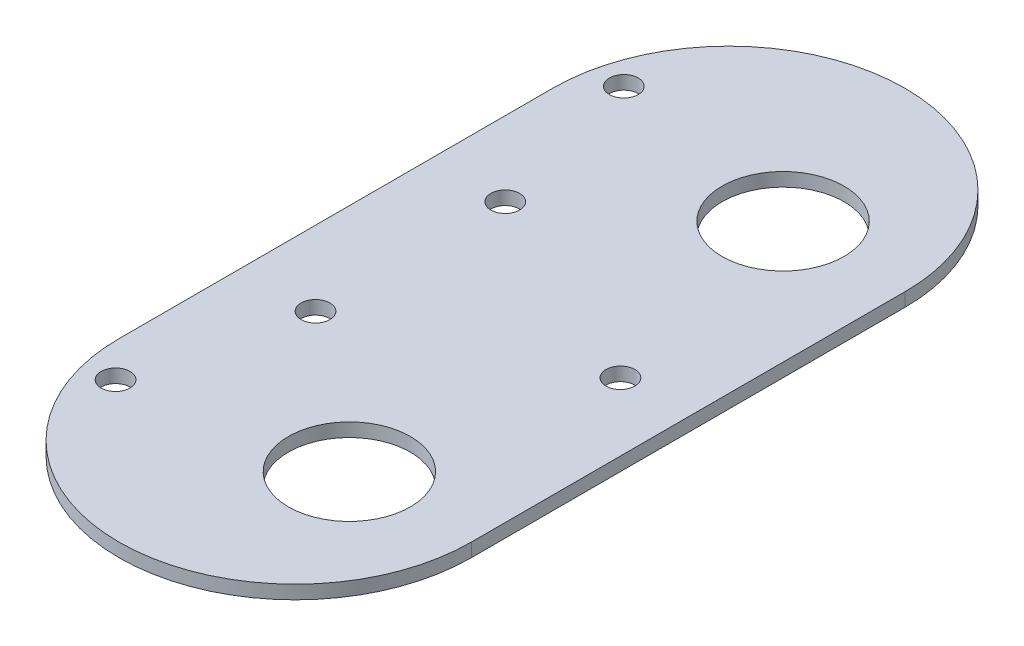
SolidWorks part; units mm, degrees
material "6061-T6 (SS)"
ref_plane "Front" through (0, 0, 0) normal (0, 0, 1) x (1, 0, 0)
ref_plane "Top" through (0, 0, 0) normal (0, 1, 0) x (1, 0, 0)
ref_plane "Right" through (0, 0, 0) normal (1, 0, 0) x (0, 0, -1)
sketch "Sketch1" plane through (0, 0, 0) normal (0, 1, 0) x (1, 0, 0)
  line L0 (0, 50.8) -> (0, -50.8) construction
  line L1 (-53.9705, 50.8) -> (-53.9705, -50.8)
  line L2 (28.5705, 50.8) -> (28.5705, -50.8)
  circle A0 centre (0, 50.8) radius 14.2875
  circle A1 centre (0, -50.8) radius 14.2875
  circle A4 centre (0, 50.8) radius 38.1 construction
  circle A5 centre (0, -50.8) radius 38.1 construction
  arc A6 (-53.9705, -50.8) -> (28.5705, -50.8) centre (-12.7, -50.8) ccw
  arc A7 (-53.9705, 50.8) -> (28.5705, 50.8) centre (-12.7, 50.8) cw
  point P4 (0, 0)
  dimension "D2" = 28.575
  dimension "D3" = 41.2705
  dimension "D4" = 76.2
  dimension "D1" = 101.6
  dimension "D5" = 12.7
extrude "Boss-Extrude1" add sketch "Sketch1" along normal blind 3.175
hole_wizard "1/4 Clearance Hole1" positions "Sketch2" profile "Sketch3" hole size "1/4" standard "ANSI Inch"
sketch "Sketch2" plane through (0, 3.175, 0) normal (0, 1, 0) x (1, 0, 0)
  line L6 (0, 50.8) -> (0, -50.8) construction
  line L7 (-36.5125, 22.225) -> (-36.5125, -22.225) construction
  line L9 (-46.0375, 59.5312) -> (-46.0375, -59.5312) construction
  point P2 (12.7, 0)
  point P4 (-46.0375, 59.5312)
  point P10 (-46.0375, -59.5312)
  point P38 (-36.5125, 22.225)
  point P40 (-36.5125, -22.225)
  point P46 (-36.5125, 0)
  point P51 (-46.0375, 0)
  dimension "D1" = 12.7
  dimension "D2" = 36.5125
  dimension "D3" = 46.0375
  dimension "D4" = 44.45
  dimension "D5" = 119.0625
sketch "Sketch3" plane through (12.7, 3.175, 0) normal (1, 0, 0) x (0, 0, 1)
  line L0 (0, 0) -> (0, 5.2048)
  line L1 (0, 5.2048) -> (3.3782, 3.175)
  line L2 (3.3782, 3.175) -> (3.3782, 0)
  line L5 (3.3782, 0) -> (0, 0)
  line L10 (0, 5.2048) -> (-3.3782, 3.175) construction
  line L11 (0, -6.35) -> (0, 107.95) construction
  dimension "Hole Dia." = 6.7564
  dimension "Hole Depth" = 3.175
  dimension "Drill Angle" = 118
